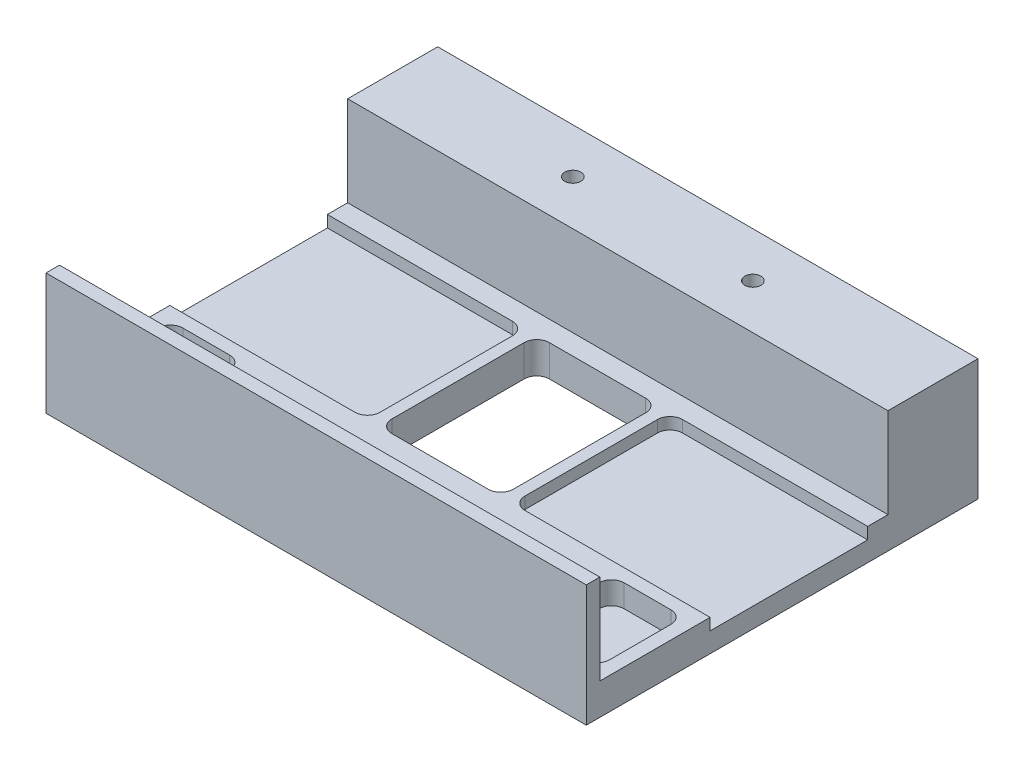
SolidWorks part; units mm, degrees
material "1345 Alloy"
ref_plane "Front Plane" through (0, 0, 0) normal (0, 0, 1) x (1, 0, 0)
ref_plane "Top Plane" through (0, 0, 0) normal (0, 1, 0) x (1, 0, 0)
ref_plane "Right Plane" through (0, 0, 0) normal (1, 0, 0) x (0, 0, -1)
sketch "Sketch1" plane through (0, 0, 0) normal (0, 1, 0) x (1, 0, 0)
  line L1 (-38.1, 22.225) -> (38.1, 22.225)
  line L2 (-38.1, 22.225) -> (-38.1, -22.225)
  line L3 (-38.1, -22.225) -> (38.1, -22.225)
  line L4 (38.1, 22.225) -> (38.1, -22.225)
  line L5 (-38.1, 22.225) -> (38.1, -22.225) construction
  line L6 (-38.1, -22.225) -> (38.1, 22.225) construction
  point P0 (0, 0)
  dimension "D1" = 44.45
  dimension "D2" = 76.2
extrude "Boss-Extrude1" add sketch "Sketch1" along normal blind 4.445
sketch "Sketch2" plane through (0, 4.445, 0) normal (0, 1, 0) x (1, 0, 0)
  line L0 (38.1, -22.225) -> (38.1, 22.225) construction
  line L1 (-38.1, 22.225) -> (38.1, 22.225)
  line L2 (-38.1, 22.225) -> (-38.1, 20.32)
  line L3 (-38.1, 20.32) -> (38.1, 20.32)
  line L4 (38.1, 22.225) -> (38.1, 20.32)
  line L5 (-38.1, 0) -> (38.1, 0) construction
  line L6 (-38.1, 22.225) -> (-38.1, -22.225) construction
  line L7 (38.1, -22.225) -> (38.1, -20.32)
  line L8 (-38.1, -20.32) -> (38.1, -20.32)
  line L9 (-38.1, -22.225) -> (-38.1, -20.32)
  line L10 (-38.1, -22.225) -> (38.1, -22.225)
  dimension "D1" = 1.905
extrude "Boss-Extrude2" add sketch "Sketch2" along normal blind 12.7
sketch "Sketch6" plane through (0, 4.445, 0) normal (0, 1, 0) x (1, 0, 0)
  line L0 (-38.1, 20.32) -> (-38.1, -20.32) construction
  line L1 (38.1, -20.32) -> (38.1, 20.32) construction
  line L2 (-38.1, 20.32) -> (38.1, 20.32) construction
  line L3 (-7.5, 16.35) -> (7.5, 16.35) construction
  line L4 (-7.5, 16.35) -> (-7.5, -3.65) construction
  line L5 (-7.5, -3.65) -> (7.5, -3.65) construction
  line L6 (7.5, 16.35) -> (7.5, -3.65) construction
  line L7 (-38.1, 6.35) -> (38.1, 6.35) construction
  line L8 (-7.5, 16.35) -> (7.5, -3.65) construction
  line L9 (-7.5, -3.65) -> (7.5, 16.35) construction
  line L10 (-38.1, -7.62) -> (38.1, -7.62) construction
  line L11 (-6.7945, -2.9845) -> (6.7945, 15.6845) construction
  line L12 (-8.5725, 15.6845) -> (-8.5725, -2.9845)
  line L13 (-6.7945, -4.7625) -> (6.7945, -4.7625)
  line L14 (8.5725, 15.6845) -> (8.5725, -2.9845)
  line L15 (-6.7945, 17.4625) -> (6.7945, 17.4625)
  line L16 (38.1, 20.32) -> (38.1, -7.62) construction
  line L17 (-38.1, 20.32) -> (-38.1, -7.62) construction
  line L18 (-6.7945, 15.6845) -> (6.7945, -2.9845) construction
  arc A0 (-6.7945, -4.7625) -> (-8.5725, -2.9845) centre (-6.7945, -2.9845) cw
  arc A1 (6.7945, -4.7625) -> (8.5725, -2.9845) centre (6.7945, -2.9845) ccw
  arc A2 (8.5725, 15.6845) -> (6.7945, 17.4625) centre (6.7945, 15.6845) ccw
  arc A3 (-6.7945, 17.4625) -> (-8.5725, 15.6845) centre (-6.7945, 15.6845) ccw
  point P0 (0, 6.35)
  point P16 (0, 6.35)
  dimension "D5" = 17.145
  dimension "D4" = 1.778
  dimension "D1" = 15
  dimension "D2" = 20
  dimension "D3" = 27.94
  dimension "D6" = 22.225
extrude "Cut-Extrude3" cut sketch "Sketch6" against normal through all
sketch "Sketch7" plane through (0, 4.445, 0) normal (0, 1, 0) x (1, 0, 0)
  line L0 (0, 6.35) -> (-38.1, 6.35) construction
  line L1 (-38.1, 20.32) -> (-38.1, -20.32) construction
  line L2 (-38.1, 17.4625) -> (-10.2235, 17.4625)
  line L3 (-38.1, 17.4625) -> (-38.1, -4.7625)
  line L4 (-38.1, -4.7625) -> (-10.2235, -4.7625)
  line L7 (0, 17.4625) -> (0, -4.7625) construction
  line L8 (-10.2235, 17.4625) -> (-10.2235, -4.7625)
  line L10 (6.7945, 17.4625) -> (-6.7945, 17.4625) construction
  line L11 (-6.7945, -4.7625) -> (6.7945, -4.7625) construction
  line L12 (-8.5725, 15.6845) -> (-8.5725, -2.9845) construction
  line L13 (10.2235, 17.4625) -> (10.2235, -4.7625)
  line L14 (38.1, 17.4625) -> (10.2235, 17.4625)
  line L16 (38.1, -4.7625) -> (10.2235, -4.7625)
  line L17 (38.1, 17.4625) -> (38.1, -4.7625)
  dimension "D2" = 1.651
extrude "Cut-Extrude4" cut sketch "Sketch7" against normal blind 1.651
sketch "Sketch11" plane through (0, 4.445, 0) normal (0, 1, 0) x (1, 0, 0)
  line L0 (0, 0) -> (0, -20.32) construction
  line L1 (-36.195, -6.604) -> (-36.195, -18.796)
  line L2 (-38.1, -4.7625) -> (-38.1, -20.32) construction
  line L3 (38.1, -20.32) -> (-38.1, -20.32) construction
  line L6 (-36.195, -18.796) -> (-26.035, -18.796)
  line L7 (-26.035, -18.796) -> (-26.035, -6.604)
  line L8 (-26.035, -6.604) -> (-36.195, -6.604)
  line L9 (-38.1, -22.225) -> (38.1, -22.225) construction
  line L10 (26.035, -6.604) -> (36.195, -6.604)
  line L11 (26.035, -18.796) -> (26.035, -6.604)
  line L12 (36.195, -18.796) -> (26.035, -18.796)
  line L13 (36.195, -6.604) -> (36.195, -18.796)
  dimension "D1" = 1.905
  dimension "D2" = 12.192
  dimension "D3" = 10.16
  dimension "D4" = 3.429
extrude "Cut-Extrude6" cut sketch "Sketch11" against normal blind 3.175
sketch "Sketch13" plane through (0, 0, -20.32) normal (0, 0, 1) x (1, 0, 0)
  line L4 (-38.1, 0) -> (38.1, 0)
  line L5 (-38.1, 17.145) -> (-38.1, 0)
  line L6 (38.1, 17.145) -> (-38.1, 17.145)
  line L7 (38.1, 0) -> (38.1, 17.145)
  line L8 (-38.1, 0) -> (38.1, 0)
  line L9 (-38.1, 17.145) -> (-38.1, 0)
  line L10 (38.1, 17.145) -> (-38.1, 17.145)
  line L11 (38.1, 0) -> (38.1, 17.145)
  dimension "D1" = 0
extrude "Boss-Extrude3" add sketch "Sketch13" against normal blind 12.7
sketch3d "3DSketch1"
  line L0 (-31.115, 4.445, 18.796) -> (-31.115, 4.445, 20.32) construction
  line L1 (-36.195, 4.445, 18.796) -> (-26.035, 4.445, 18.796) construction
  line L2 (38.1, 4.445, 20.32) -> (-38.1, 4.445, 20.32) construction
  line L3 (-31.115, 4.445, 20.32) -> (-31.115, 17.145, 20.32) construction
  line L4 (38.1, 17.145, 20.32) -> (-38.1, 17.145, 20.32) construction
fillet "Fillet1" radius 1.778 12 edges at (-36.195, 2.8575, 6.604) (-26.035, 2.8575, 6.604) (26.035, 2.8575, 18.796) (36.195, 2.8575, 18.796) (26.035, 2.8575, 6.604) (36.195, 2.8575, 6.604) (-36.195, 2.8575, 18.796) (-26.035, 2.8575, 18.796) (-10.2235, 3.6195, 4.7625) (-10.2235, 3.6195, -17.4625) (10.2235, 3.6195, -17.4625) (10.2235, 3.6195, 4.7625)
hole_wizard "1/4-20 Tapped Hole1" positions "Sketch16" profile "Sketch15" tap size "1/4-20" standard "Ansi Inch"
sketch "Sketch16" plane through (0, 0, -33.02) normal (0, 0, -1) x (-1, 0, 0)
  line L0 (0, 0) -> (0, 17.145) construction
  line L1 (38.1, 0) -> (-38.1, 0) construction
  line L2 (-38.1, 17.145) -> (38.1, 17.145) construction
  line L4 (0, 8.5725) -> (-38.1, 8.5725) construction
  line L5 (-38.1, 0) -> (-38.1, 17.145) construction
  point P0 (-25.4521, 8.5725)
  point P16 (25.4521, 8.5725)
sketch "Sketch15" plane through (25.4521, 8.5725, -33.02) normal (1, 0, 0) x (0, 1, 0)
  line L0 (0, 0) -> (0, 7.8838)
  line L1 (0, 7.8838) -> (2.5527, 6.35)
  line L2 (2.5527, 6.35) -> (2.5527, 0)
  line L5 (2.5527, 0) -> (0, 0)
  line L10 (0, 7.8838) -> (-2.5527, 6.35) construction
  line L11 (0, -6.35) -> (0, 107.95) construction
  dimension "Tap Drill Dia." = 5.1054
  dimension "Tap Drill Depth" = 6.35
  dimension "Drill Angle" = 118
cosmetic thread "Hole Thread1" parameters "D1"=6.35, "D2"=6.35
cosmetic thread "Hole Thread2" parameters "D1"=6.35, "D2"=6.35
hole_wizard "#4-40 Tapped Hole1" positions "Sketch18" profile "Sketch17" tap size "#4-40" standard "Ansi Inch"
sketch "Sketch18" plane through (0, 17.145, 0) normal (0, 1, 0) x (-1, 0, 0)
  point P6 (12.7, -26.67)
  point P10 (-12.7, -26.67)
sketch "Sketch17" plane through (-12.7, 17.145, -26.67) normal (1, 0, 0) x (0, 0, 1)
  line L0 (0, 0) -> (0, 7.0292)
  line L1 (0, 7.0292) -> (1.1303, 6.35)
  line L2 (1.1303, 6.35) -> (1.1303, 0)
  line L5 (1.1303, 0) -> (0, 0)
  line L10 (0, 7.0292) -> (-1.1303, 6.35) construction
  line L11 (0, -6.35) -> (0, 107.95) construction
  dimension "Tap Drill Dia." = 2.2606
  dimension "Tap Drill Depth" = 6.35
  dimension "Drill Angle" = 118
cosmetic thread "Hole Thread3" parameters "D1"=6.35, "D2"=2.8448
cosmetic thread "Hole Thread4" parameters "D1"=6.35, "D2"=2.8448
sketch "refSketch" plane through (0, 4.445, 0) normal (0, 1, 0) x (1, 0, 0)
  line L0 (-6.7945, 15.6845) -> (6.7945, -2.9845) construction
  line L1 (-6.7945, -2.9845) -> (6.7945, 15.6845) construction
  point P8 (0, 6.35)
ref_axis "Axis1" through (0, -44.4835, -6.35) along (0, 1, 0)
